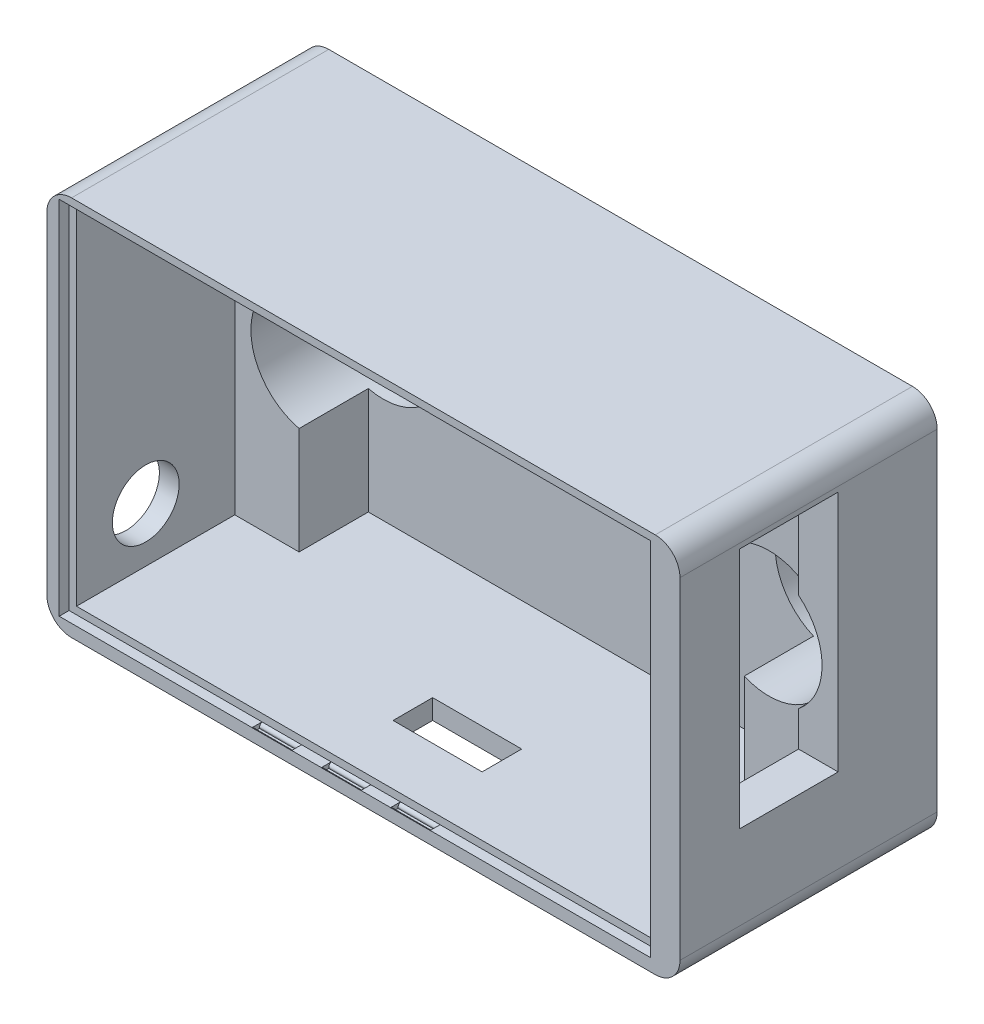
SolidWorks part; units mm, degrees
ref_plane "Front Plane" through (0, 0, 0) normal (0, 0, 1) x (1, 0, 0)
ref_plane "Top Plane" through (0, 0, 0) normal (0, 1, 0) x (1, 0, 0)
ref_plane "Right Plane" through (0, 0, 0) normal (1, 0, 0) x (0, 0, -1)
sketch "Sketch1" plane through (0, 0, 0) normal (0, 0, 1) x (1, 0, 0)
  line L1 (0, 0) -> (64, 0)
  line L2 (0, 0) -> (0, 38.5)
  line L3 (0, 38.5) -> (64, 38.5)
  line L4 (64, 0) -> (64, 38.5)
  dimension "D1" = 64
  dimension "D2" = 38.5
extrude "Boss-Extrude1" add sketch "Sketch1" along normal blind 26
sketch "Sketch2" plane through (0, 0, 26) normal (0, 0, 1) x (1, 0, 0)
  line L0 (64, 38.5) -> (0, 38.5) construction
  line L1 (2, 37) -> (60, 37)
  line L2 (2, 37) -> (2, 2)
  line L3 (2, 2) -> (60, 2)
  line L4 (60, 37) -> (60, 2)
  line L6 (0, 38.5) -> (0, 0) construction
  dimension "D1" = 35
  dimension "D2" = 1.5
  dimension "D3" = 2
  dimension "D4" = 58
extrude "Cut-Extrude1" cut sketch "Sketch2" against normal blind 17
sketch "Sketch4" plane through (0, 0, 9) normal (0, 0, 1) x (1, 0, 0)
  line L1 (8.5, 37) -> (53.5, 37)
  line L2 (8.5, 37) -> (8.5, 2)
  line L3 (8.5, 2) -> (53.5, 2)
  line L4 (53.5, 37) -> (53.5, 2)
  line L5 (2, 2) -> (60, 2) construction
  line L6 (2, 37) -> (2, 2) construction
  dimension "D1" = 35
  dimension "D2" = 45
  dimension "D3" = 0
  dimension "D4" = 6.5
extrude "Cut-Extrude3" cut sketch "Sketch4" against normal blind 7
sketch "Sketch5" plane through (0, 0, 0) normal (0, 0, -1) x (-1, 0, 0)
  line L0 (-64, 0) -> (-64, 38.5) construction
  line L2 (-64, 38.5) -> (0, 38.5) construction
  circle A0 centre (-56, 19.5) radius 6.375
  circle A1 centre (-10.0027, 19.0054) radius 6.375
  dimension "D1" = 12.75
  dimension "D2" = 12.75
  dimension "D4" = 8
  dimension "D5" = 19
  dimension "D3" = 46
extrude "Cut-Extrude4" cut sketch "Sketch5" against normal blind 12
sketch "Sketch6" plane through (64, 0, 0) normal (1, 0, 0) x (0, 0, -1)
  line L0 (-26, 0) -> (-26, 38.5) construction
  line L1 (-20, 35.5) -> (-10.0107, 35.5)
  line L2 (-20, 35.5) -> (-20, 11)
  line L3 (-20, 11) -> (-10.0107, 11)
  line L4 (-10.0107, 35.5) -> (-10.0107, 11)
  line L5 (-26, 38.5) -> (0, 38.5) construction
  dimension "D1" = 6
  dimension "D2" = 3
  dimension "D3" = 24.5
extrude "Cut-Extrude5" cut sketch "Sketch6" against normal blind 17
sketch "Sketch7" plane through (0, 0, 0) normal (-1, 0, 0) x (0, 0, 1)
  line L0 (26, 38.5) -> (26, 0) construction
  line L1 (26, 38.5) -> (0, 38.5) construction
  circle A0 centre (18, 7.5) radius 3.375
  dimension "D1" = 6.75
  dimension "D3" = 31
  dimension "D2" = 8
extrude "Cut-Extrude6" cut sketch "Sketch7" against normal blind 7
sketch "Sketch8" plane through (0, 0, 0) normal (0, -1, 0) x (1, 0, 0)
  line L0 (64, 26) -> (64, 0) construction
  line L1 (28, 19) -> (37, 19)
  line L2 (28, 19) -> (28, 15)
  line L3 (28, 15) -> (37, 15)
  line L4 (37, 19) -> (37, 15)
  line L7 (0, 0) -> (64, 0) construction
  dimension "D1" = 9
  dimension "D2" = 4
  dimension "D3" = 27
  dimension "D4" = 15
extrude "Cut-Extrude7" cut sketch "Sketch8" against normal blind 7
fillet "Fillet1" radius 2.5 4 edges at (64, 38.5, 13) (64, 0, 13) (0, 0, 13) (0, 38.5, 13)
sketch "Sketch10" plane through (0, 0, 26) normal (0, 0, 1) x (1, 0, 0)
  line L0 (53.5, 37) -> (8.5, 37) construction
  line L1 (1.5, 37.75) -> (61, 37.75)
  line L2 (1.5, 37.75) -> (1.5, 37)
  line L3 (1.5, 37) -> (61, 37)
  line L4 (61, 37.75) -> (61, 37)
  line L6 (60, 2) -> (60, 37) construction
  line L8 (2, 37) -> (2, 2) construction
  dimension "D1" = 0.75
  dimension "D2" = 0
  dimension "D3" = 1
  dimension "D4" = 0.5
extrude "Cut-Extrude8" cut sketch "Sketch10" against normal blind 1
sketch "Sketch11" plane through (0, 0, 26) normal (0, 0, 1) x (1, 0, 0)
  line L0 (2, 2) -> (60, 2) construction
  line L1 (1.25, 2) -> (61, 2)
  line L2 (1.25, 2) -> (1.25, 1.25)
  line L3 (1.25, 1.25) -> (61, 1.25)
  line L4 (61, 2) -> (61, 1.25)
  line L5 (2, 37) -> (2, 2) construction
  line L6 (60, 2) -> (60, 14.5361) construction
  dimension "D1" = 0
  dimension "D2" = 0.75
  dimension "D3" = 0.75
  dimension "D4" = 1
extrude "Cut-Extrude9" cut sketch "Sketch11" against normal blind 1
sketch "Sketch12" plane through (0, 0, 26) normal (0, 0, 1) x (1, 0, 0)
  line L0 (60, 2) -> (60, 37) construction
  line L1 (61, 1.25) -> (60, 1.25)
  line L2 (61, 1.25) -> (61, 37.75)
  line L3 (61, 37.75) -> (60, 37.75)
  line L4 (60, 1.25) -> (60, 37.75)
  line L5 (2, 37) -> (2, 2) construction
  line L6 (1.25, 1.25) -> (2, 1.25)
  line L7 (1.25, 1.25) -> (1.25, 37.75)
  line L8 (1.25, 37.75) -> (2, 37.75)
  line L9 (2, 1.25) -> (2, 37.75)
  line L10 (2, 37) -> (60, 37) construction
  line L11 (1.25, 1.25) -> (61, 1.25) construction
  line L12 (61, 37.75) -> (1.5, 37.75) construction
  point P16 (60.5, 37.75)
  dimension "D1" = 0
  dimension "D2" = 0
  dimension "D3" = 0.75
  dimension "D4" = 0.75
  dimension "D5" = 0
  dimension "D6" = 1
  dimension "D7" = 0
  dimension "D8" = 0
extrude "Cut-Extrude10" cut sketch "Sketch12" against normal blind 1
sketch "Sketch13" plane through (0, 1.25, 0) normal (0, 1, 0) x (1, 0, 0)
  line L0 (1.25, -26) -> (61, -26) construction
  line L1 (31.75, -25.7) -> (27.75, -25.7)
  line L2 (31.75, -25.7) -> (31.75, -25.25)
  line L3 (31.75, -25.25) -> (27.75, -25.25)
  line L4 (27.75, -25.7) -> (27.75, -25.25)
  line L5 (24.75, -25.7) -> (20.75, -25.7)
  line L6 (24.75, -25.7) -> (24.75, -25.25)
  line L7 (24.75, -25.25) -> (20.75, -25.25)
  line L8 (20.75, -25.7) -> (20.75, -25.25)
  line L9 (38.75, -25.7) -> (34.75, -25.7)
  line L10 (38.75, -25.7) -> (38.75, -25.25)
  line L11 (38.75, -25.25) -> (34.75, -25.25)
  line L12 (34.75, -25.7) -> (34.75, -25.25)
  line L13 (1.25, -25) -> (61, -25) construction
  line L17 (1.25, -25) -> (1.25, -26) construction
  line L18 (61, -25) -> (61, -26) construction
  point P20 (1.25, -25.5)
  dimension "D1" = 4
  dimension "D2" = 3
  dimension "D3" = 3
  dimension "D4" = 0.45
  dimension "D5" = 4
  dimension "D6" = 0.45
  dimension "D7" = 0.3
  dimension "D8" = 0.25
  dimension "D9" = 19.5
  dimension "D10" = 22.25
  dimension "D12" = 4
extrude "Cut-Extrude11" cut sketch "Sketch13" against normal blind 0.45
fillet "Fillet2" radius 0.4 6 edges at (22.75, 1.25, 25.25) (22.75, 1.25, 25.7) (29.75, 1.25, 25.25) (29.75, 1.25, 25.7) (36.75, 1.25, 25.7) (36.75, 1.25, 25.25)
sketch "Sketch14" plane through (0, 37.75, 0) normal (0, -1, 0) x (1, 0, 0)
  line L0 (61, 25) -> (61, 26) construction
  line L1 (27.75, 25.7) -> (31.75, 25.7)
  line L2 (27.75, 25.7) -> (27.75, 25.25)
  line L3 (27.75, 25.25) -> (31.75, 25.25)
  line L4 (31.75, 25.7) -> (31.75, 25.25)
  line L5 (34.75, 25.7) -> (38.75, 25.7)
  line L6 (34.75, 25.7) -> (34.75, 25.25)
  line L7 (34.75, 25.25) -> (38.75, 25.25)
  line L8 (38.75, 25.7) -> (38.75, 25.25)
  line L9 (24.75, 25.7) -> (20.75, 25.7)
  line L10 (24.75, 25.7) -> (24.75, 25.25)
  line L11 (24.75, 25.25) -> (20.75, 25.25)
  line L12 (20.75, 25.7) -> (20.75, 25.25)
  line L13 (61, 26) -> (1.25, 26) construction
  dimension "D1" = 4
  dimension "D2" = 4
  dimension "D3" = 4
  dimension "D4" = 3
  dimension "D5" = 3
  dimension "D6" = 22.25
  dimension "D7" = 0.45
  dimension "D8" = 0.3
  dimension "D9" = 0.45
  dimension "D10" = 0.3
  dimension "D11" = 0.45
  dimension "D12" = 0.3
extrude "Cut-Extrude12" cut sketch "Sketch14" against normal blind 0.45
fillet "Fillet3" radius 0.4 6 edges at (36.75, 37.75, 25.7) (36.75, 37.75, 25.25) (29.75, 37.75, 25.25) (29.75, 37.75, 25.7) (22.75, 37.75, 25.7) (22.75, 37.75, 25.25)
